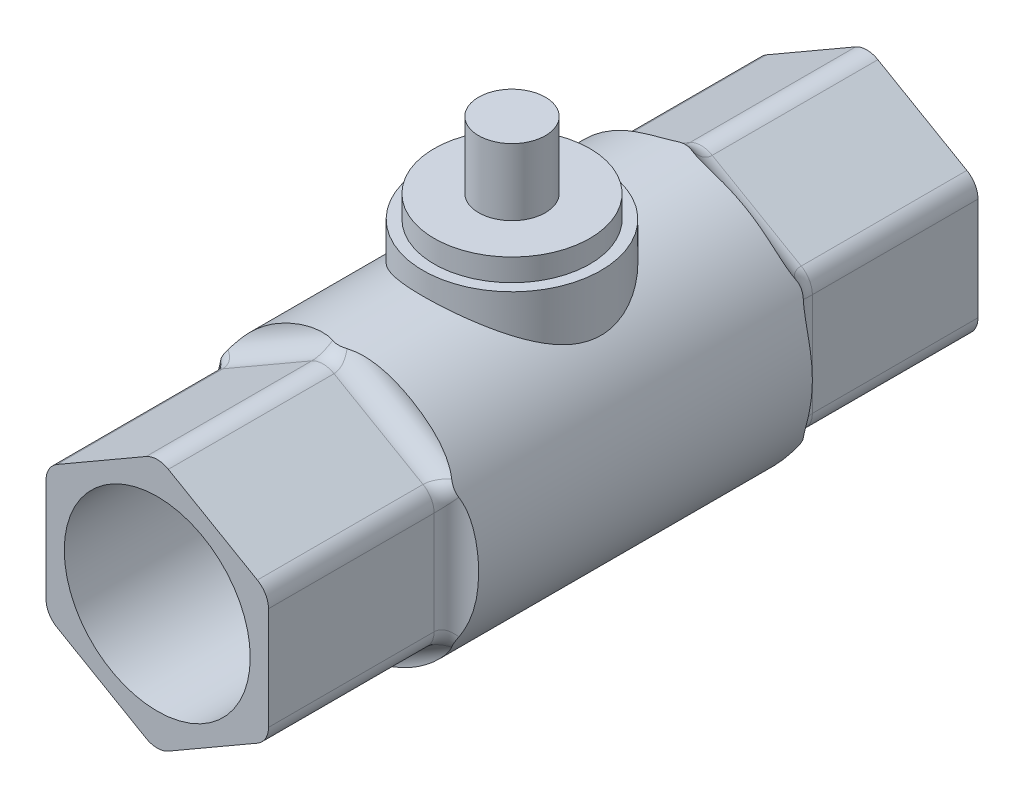
SolidWorks part; units mm, degrees
material "Brass"
ref_plane "Front Plane" through (0, 0, 0) normal (0, 0, 1) x (1, 0, 0)
ref_plane "Top Plane" through (0, 0, 0) normal (0, 1, 0) x (1, 0, 0)
ref_plane "Right Plane" through (0, 0, 0) normal (1, 0, 0) x (0, 0, -1)
sketch "Sketch1" plane through (0, 0, 0) normal (0, 0, 1) x (1, 0, 0)
  line L1 (0, 14.6647) -> (-12.7, 7.3323)
  line L2 (-12.7, 7.3323) -> (-12.7, -7.3323)
  line L3 (-12.7, -7.3323) -> (0, -14.6647)
  line L4 (0, -14.6647) -> (12.7, -7.3323)
  line L5 (12.7, -7.3323) -> (12.7, 7.3323)
  line L6 (12.7, 7.3323) -> (0, 14.6647)
  circle A0 centre (0, 0) radius 12.7 construction
  circle A1 centre (0, 0) radius 10.6171
  dimension "D1" = 25.4
  dimension "D2" = 21.2341
extrude "Boss-Extrude1" add sketch "Sketch1" along normal blind 81
ref_plane "Plane1" through (0, 0, 40.5) normal (0, 0, 1) x (1, 0, 0)
sketch "Sketch2" plane through (0, 0, 40.5) normal (0, 0, 1) x (1, 0, 0)
  circle A0 centre (0, 0) radius 10.6171
  circle A1 centre (0, 0) radius 15.24
  circle A2 centre (0, 0) radius 10.6171 construction
  dimension "D1" = 30.48
extrude "Boss-Extrude2" add sketch "Sketch2" along normal mid plane 38.1
fillet "Fillet1" radius 2.54 12 edges at (-6.35, -10.9985, 21.45) (6.35, -10.9985, 21.45) (12.7, 0, 21.45) (6.35, 10.9985, 21.45) (-6.35, 10.9985, 21.45) (-12.7, 0, 21.45) (-12.7, 0, 59.55) (-6.35, -10.9985, 59.55) (6.35, -10.9985, 59.55) (12.7, 0, 59.55) (6.35, 10.9985, 59.55) (-6.35, 10.9985, 59.55)
fillet "Fillet2" radius 2.54 24 edges at (-12.8278, 7.4061, 61.2945) (-12.8278, -7.4061, 61.2945) (0, -14.8122, 61.2945) (12.8278, -7.4061, 61.2945) (0, 14.8122, 61.2945) (12.8278, 7.4061, 61.2945) (12.8278, -7.4061, 19.7055) (0, -14.8122, 19.7055) (-12.8278, -7.4061, 19.7055) (-12.8278, 7.4061, 19.7055) (0, 14.8122, 19.7055) (12.8278, 7.4061, 19.7055) (-12.7, 7.3323, 71.545) (-12.7, -7.3323, 71.545) (0, -14.6647, 71.545) (12.7, -7.3323, 71.545) (0, 14.6647, 71.545) (12.7, 7.3323, 71.545) (12.7, -7.3323, 9.455) (0, -14.6647, 9.455) (-12.7, -7.3323, 9.455) (-12.7, 7.3323, 9.455) (0, 14.6647, 9.455) (12.7, 7.3323, 9.455)
sketch "Sketch3" plane through (0, 0, 40.5) normal (0, 0, 1) x (1, 0, 0)
  line L0 (0, 0) -> (0, 39.75) construction
  line L1 (3.81, 20.32) -> (8.89, 20.32)
  line L2 (0, 11.3592) -> (10.16, 11.3592)
  line L4 (8.89, 17.78) -> (10.16, 17.78)
  line L5 (10.16, 11.3592) -> (10.16, 17.78)
  line L9 (8.89, 17.78) -> (8.89, 20.32)
  line L11 (0, 11.3592) -> (0, 27.94)
  line L12 (0, 27.94) -> (3.81, 27.94)
  line L13 (3.81, 20.32) -> (3.81, 27.94)
  arc A0 (12.7667, 8.3228) -> (7.62, 13.1982) centre (0, 0) ccw construction
  arc A1 (0.8244, 15.2177) -> (-0.8244, 15.2177) centre (0, 0) ccw construction
  point P5 (0, 0)
  point P8 (8.89, 19.05)
  point P13 (0, 21.2843)
  point P17 (0, 21.1926)
  point P18 (0, 14.0206)
  dimension "D3" = 17.78
  dimension "D1" = 39.75
  dimension "D2" = 10.16
  dimension "D4" = 8.89
  dimension "D5" = 2.54
  dimension "D6" = 7.62
  dimension "D7" = 3.81
revolve "Revolve1" add sketch "Sketch3" angle 360 about L0
